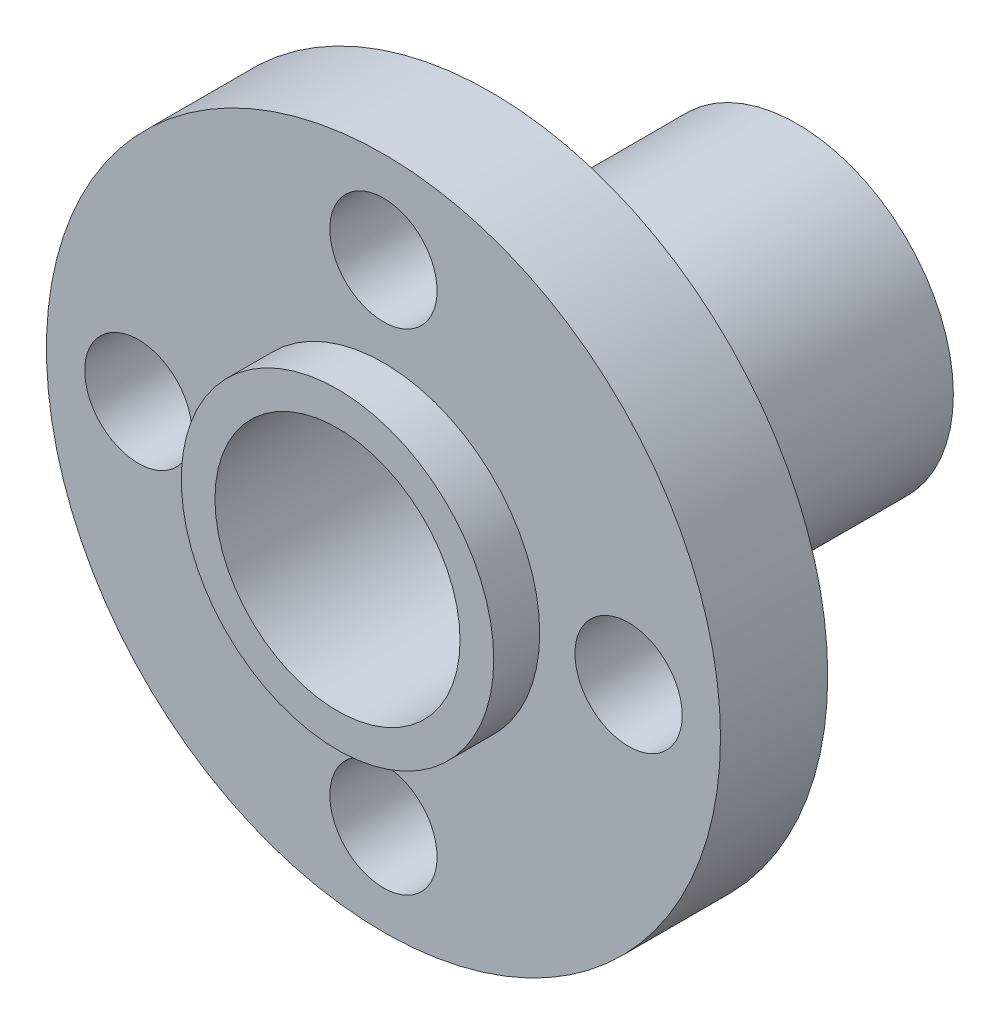
SolidWorks part; units mm, degrees
material "Brass"
ref_plane "Front Plane" through (0, 0, 0) normal (0, 0, 1) x (1, 0, 0)
ref_plane "Top Plane" through (0, 0, 0) normal (0, 1, 0) x (1, 0, 0)
ref_plane "Right Plane" through (0, 0, 0) normal (1, 0, 0) x (0, 0, -1)
sketch "Sketch1" plane through (0, 0, 0) normal (0, 0, 1) x (1, 0, 0)
  circle A0 centre (0, 0) radius 11
  circle A1 centre (0, 0) radius 8
  circle A2 centre (0, 8) radius 1.75
  circle A3 centre (8, 0) radius 1.75
  circle A4 centre (0, -8) radius 1.75
  circle A5 centre (-8, 0) radius 1.75
  circle A6 centre (0, 0) radius 4
  point P15 (0, 0)
  dimension "D1" = 22
  dimension "D2" = 16
  dimension "D3" = 3.5
  dimension "D5" = 8
  dimension "D4" = 4
extrude "Boss-Extrude1" add sketch "Sketch1" along normal blind 3.5 contours A0 A5 A1 A2 A3 A4 | A5 A1 A4 A3 A2 A6 region at (-10.6889, 0, 0) region at (6.0291, 0, 0)
sketch "Sketch2" plane through (0, 0, 0) normal (0, 0, -1) x (-1, 0, 0)
  circle A0 centre (0, 0) radius 5.1
  circle A1 centre (0, 0) radius 4
  dimension "D1" = 10.2
  dimension "D2" = 8
extrude "Boss-Extrude2" add sketch "Sketch2" along normal blind 10
sketch "Sketch3" plane through (0, 0, 3.5) normal (0, 0, 1) x (1, 0, 0)
  circle A0 centre (0, 0) radius 5.1
  circle A1 centre (0, 0) radius 4
  dimension "D1" = 10.2
  dimension "D2" = 8
extrude "Boss-Extrude3" add sketch "Sketch3" along normal blind 1.5
